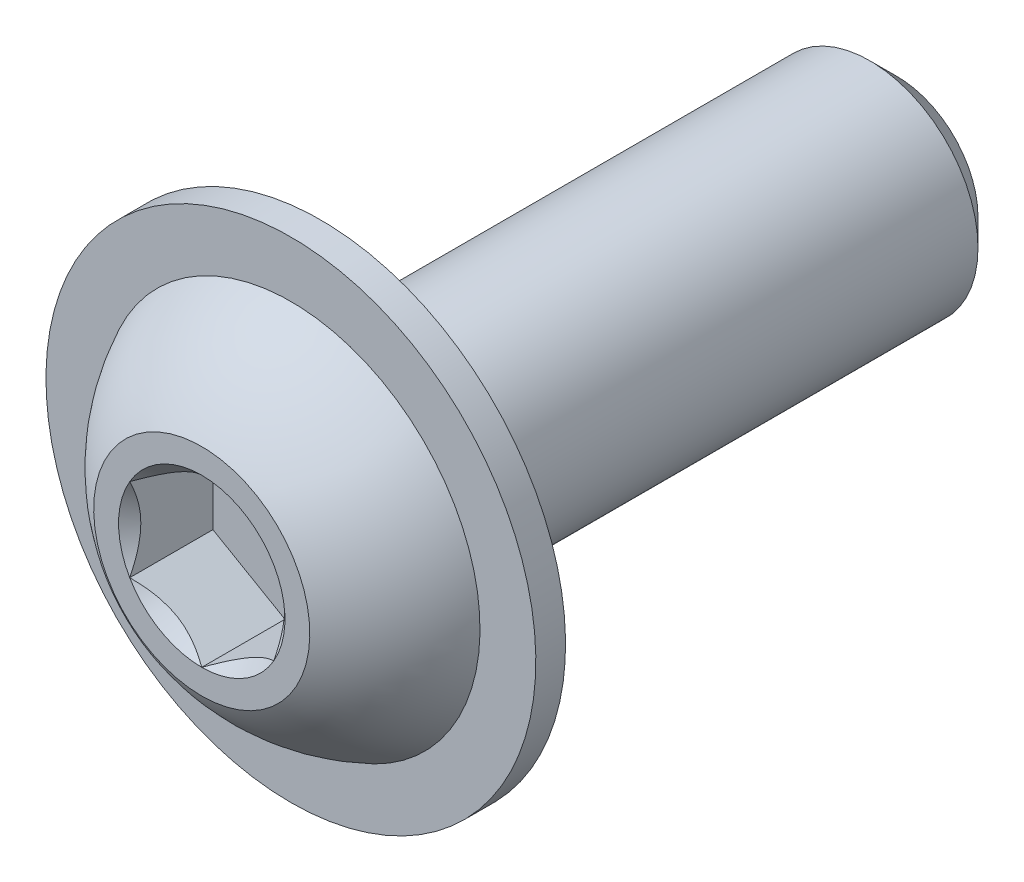
SolidWorks part; units mm, degrees
ref_plane "Front" through (0, 0, 0) normal (0, 0, 1) x (1, 0, 0)
ref_plane "Top" through (0, 0, 0) normal (0, 1, 0) x (1, 0, 0)
ref_plane "Right" through (0, 0, 0) normal (1, 0, 0) x (0, 0, -1)
sketch "Sketch1" plane through (0, 0, 0) normal (1, 0, 0) x (0, 0, -1)
  line L2 (-6.35, 3) -> (9.65, 3)
  line L3 (9.65, 3) -> (9.65, 0)
  line L4 (9.65, -3) -> (8.65, -3) construction
  line L6 (-7.175, 5.25) -> (-6.35, 5.25) construction
  line L7 (9.65, 3) -> (9.65, -3) construction
  line L8 (-9.65, 0) -> (9.65, 0) construction
  line L9 (-6.35, 5.25) -> (-6.35, -5.25) construction
  line L11 (-6.35, 3) -> (-6.35, 0)
  line L13 (-9.65, 2) -> (-9.65, -2) construction
  line L14 (-9.65, 2) -> (-9.65, 3) construction
  line L15 (-7.175, 5.25) -> (-7.175, 6.8) construction
  line L16 (-7.175, 6.8) -> (-6.35, 6.8) construction
  line L17 (-6.35, 6.8) -> (-6.35, 5.25) construction
  line L18 (-6.35, 6.8) -> (-6.35, -6.8) construction
  arc A3 (-9.65, 3) -> (-7.175, 5.25) centre (-4.6625, 0) cw construction
  point P16 (6.15, -3)
  point P24 (0, 0)
  dimension "Thread OD" = 6
  dimension "D1" = 0.825
  dimension "Head Height" = 3.3
  dimension "Head Diameter" = 10.5
  dimension "Length" = 16
  dimension "Drive Size" = 4
  dimension "Flange Diameter" = 13.6
  dimension "D2" = 3.5
  dimension "Thread Pitch" = 1
sketch "Sketch13" plane through (0, 0, 0) normal (1, 0, 0) x (0, 0, -1)
  line L1 (-6.35, 3) -> (9.65, 3)
  line L2 (-6.35, 3) -> (-6.35, 0)
  line L3 (-6.35, 0) -> (9.65, 0)
  line L4 (9.65, 3) -> (9.65, 0)
revolve "Revolve1" add sketch "Sketch13" angle 360 about L8
chamfer "Chamfer1" distance 0.75 angle 45 1 edges at (3, 0, -9.65)
sketch "Sketch7" plane through (0, 0, 0) normal (1, 0, 0) x (0, 0, -1)
  line L0 (-6.35, 5.25) -> (-6.35, -5.25) construction
  line L1 (-6.35, 5.25) -> (-6.35, 0)
  line L2 (-7.175, 5.25) -> (-7.175, 6.8)
  line L3 (-7.175, 6.8) -> (-6.35, 6.8)
  line L4 (-6.35, 6.8) -> (-6.35, 5.25)
  line L6 (-7.175, 5.25) -> (-6.35, 5.25) construction
  line L8 (-9.65, 0) -> (9.65, 0) construction
  line L12 (-7.175, 5.25) -> (-6.35, 5.25) construction
  line L13 (-9.65, 0) -> (-6.35, 0)
  line L14 (-9.65, 2) -> (-9.65, -2) construction
  line L16 (-9.65, 3) -> (-9.65, 0)
  arc A2 (-7.175, 5.25) -> (-9.65, 3) centre (-4.6625, 0) ccw construction
  arc A3 (-7.175, 5.25) -> (-9.65, 3) centre (-4.6625, 0) ccw
revolve "Revolve2" add sketch "Sketch7" angle 360 mid plane about L13
sketch "Sketch5" plane through (0, 0, 9.65) normal (0, 0, 1) x (1, 0, 0)
  line L1 (2, -1.1547) -> (2, 1.1547)
  line L2 (2, 1.1547) -> (0, 2.3094)
  line L3 (0, 2.3094) -> (-2, 1.1547)
  line L4 (-2, 1.1547) -> (-2, -1.1547)
  line L5 (-2, -1.1547) -> (0, -2.3094)
  line L6 (0, -2.3094) -> (2, -1.1547)
  circle A0 centre (0, 0) radius 2 construction
extrude "Cut-Extrude2" cut sketch "Sketch5" against normal blind 2.31
sketch "Sketch6" plane through (0, 0, 9.65) normal (0, 0, 1) x (1, 0, 0)
  circle A0 centre (0, 0) radius 2.3094
extrude "Cut-Extrude3" cut sketch "Sketch6" against normal blind 2.31 draft 45
split "Split1" [suppressed] bodies to split 113
sketch "Sketch14" [suppressed] plane through (0, 0, -9.65) normal (0, 0, -1) x (-1, 0, 0)
  circle A0 centre (0, 0) radius 3 construction
  circle A1 centre (0, 0) radius 3
curve "Helix/Spiral1" [suppressed] pitch 1 height 17 turns 17
sketch "Sketch16" [suppressed] plane through (0, 0, 0) normal (1, 0, 0) x (0, 0, -1)
  line L0 (10.5875, 3.1083) -> (9.5875, 3.1083) construction
  line L1 (9.5875, 3.1083) -> (10.0875, 2.2422) construction
  line L2 (10.0875, 2.2422) -> (10.5875, 3.1083) construction
  line L3 (10.525, 3) -> (9.65, 3) construction
  line L4 (10.0875, 3.1083) -> (10.0875, 3) construction
  line L5 (10.5563, 3.0541) -> (9.6187, 3.0541) construction
  line L6 (10.15, 2.3505) -> (10.025, 2.3505) construction
  line L7 (10.0875, 2.3505) -> (10.0875, 2.2422) construction
  line L8 (10.025, 2.3505) -> (9.6187, 3.0541)
  line L9 (9.6187, 3.0541) -> (10.5563, 3.0541)
  line L10 (10.5563, 3.0541) -> (10.15, 2.3505)
  line L11 (10.15, 2.3505) -> (10.025, 2.3505)
  point P11 (10.0875, 3.0541)
  dimension "D1" = 1
  dimension "D2" = 0.125
sweep "Cut-Sweep1" [suppressed] cut profiles "Sketch16" path "Helix/Spiral1"
sketch "Sketch17" [suppressed] plane through (0, 0, 6.35) normal (0, 0, -1) x (-1, 0, 0)
  circle A1 centre (0, 0) radius 3
  circle A2 centre (0, 0) radius 3
  dimension "D1" = 0
extrude "Boss-Extrude1" [suppressed] add sketch "Sketch17" along normal up to next draft 20
equation "\"D3@Helix/Spiral1\" = \"Length@Sketch1\" + \"D4@Helix/Spiral1\""
equation "\"D1@Chamfer1\" = \"D4@Helix/Spiral1\" * .75"
equation "\"D1@Cut-Extrude2\" = \"Head Height@Sketch1\" * .7"
equation "\"D1@Sketch1\" = \"Head Height@Sketch1\" * .25"
equation "\"D1@Cut-Extrude3\" = \"D1@Cut-Extrude2\""
equation "\"D2@Sketch1\"=\"D4@Helix/Spiral1\"*3.5"
equation "\"D4@Helix/Spiral1\"=\"Thread Pitch@Sketch1\""
equation "\"D1@Sketch16\"=\"Thread Pitch@Sketch1\""
equation "\"D2@Sketch16\"=\"D1@Sketch16\"/8"
